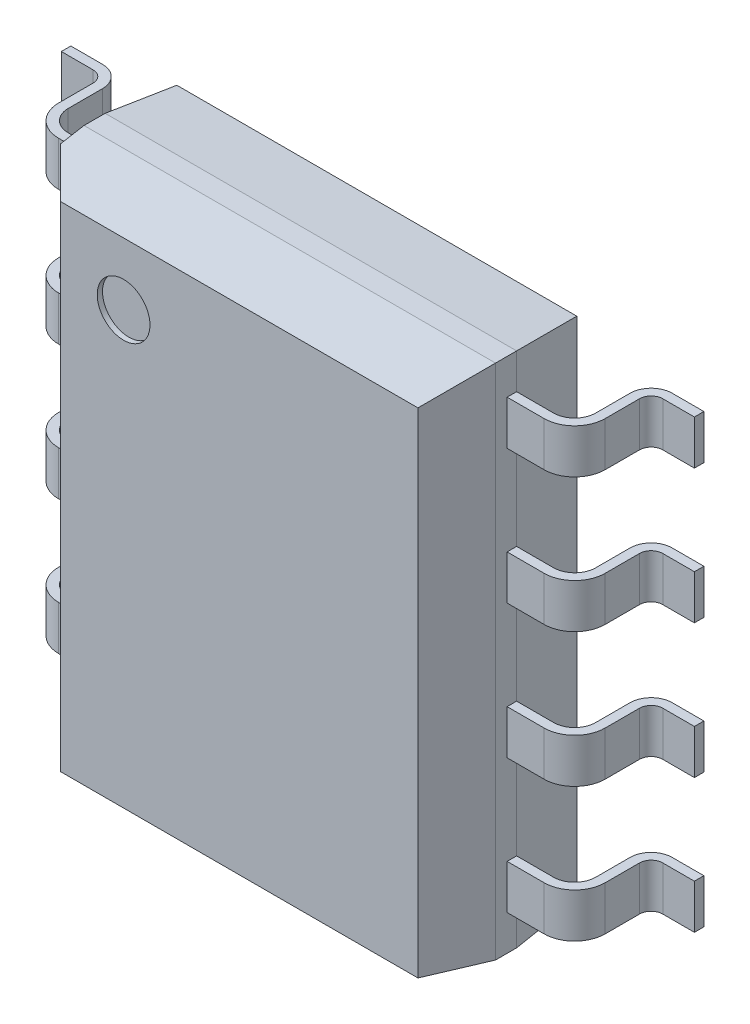
SolidWorks part; units mm, degrees
ref_plane "Face" through (0, 0, 0) normal (0, 0, 1) x (1, 0, 0)
ref_plane "Dessus" through (0, 0, 0) normal (0, 1, 0) x (1, 0, 0)
ref_plane "Droite" through (0, 0, 0) normal (1, 0, 0) x (0, 0, -1)
ref_plane "fond circuit" through (0, 0, 0.1) normal (0, 0, 1) x (1, 0, 0)
sketch "Esquisse2" plane through (0, 0, 0.1) normal (0, 0, 1) x (1, 0, 0)
  line L1 (-1.95, 2.45) -> (1.95, 2.45)
  line L2 (-1.95, 2.45) -> (-1.95, -2.45)
  line L3 (-1.95, -2.45) -> (1.95, -2.45)
  line L4 (1.95, 2.45) -> (1.95, -2.45)
  point P4 (1.95, 0)
  point P6 (0, 2.45)
  dimension "D1" = 3.9
  dimension "D2" = 4.9
extrude "corp" add sketch "Esquisse2" along normal blind 1.45
ref_plane "plan pin 1" through (0, 1.905, 0) normal (0, 1, 0) x (-1, 0, 0)
sketch "Esquisse6" plane through (0, 1.905, 0) normal (0, 1, 0) x (-1, 0, 0)
  line L0 (0, 0) -> (6.8831, 0) construction
  line L1 (1.95, 0.725) -> (2.3, 0.725)
  line L2 (1.95, 1.55) -> (1.95, 0.1) construction
  line L3 (2.5, 0.525) -> (2.5, 0.2)
  line L4 (3, 0) -> (2.7, 0)
  line L6 (-1.95, 1.55) -> (1.95, 1.55) construction
  arc A0 (2.3, 0.725) -> (2.5, 0.525) centre (2.3, 0.525) cw
  arc A1 (2.7, 0) -> (2.5, 0.2) centre (2.7, 0.2) cw
  dimension "D1" = 0.2
  dimension "D2" = 0.5
  dimension "D3" = 1.05
  dimension "D4" = 0.825
extrude "pin 1" add sketch "Esquisse6" along normal mid plane 0.42 thin thin type one direction wall 0.09
pattern_linear "Répétition pin 1-4" count 4 spacing 1.27 along (0, -1, 0) of "pin 1"
mirror "Symétrie1" about plane through (0, 0, 0) normal (1, 0, 0) of "Répétition pin 1-4"
ref_plane "Plan2" through (3.75, 0, 0) normal (1, 0, 0) x (0, 0, -1)
chamfer "Chanfrein4" distance 0.625 angle 10 3 edges at (0, 2.45, 1.55) (1.95, 0, 1.55) (0, -2.45, 1.55) first distance on face at (0, 2.45, 0.825) first distance on face at (1.95, -1.905, 0.77) first distance on face at (0, -2.45, 0.825)
chamfer "Chanfrein5" distance 0.625 angle 5 4 edges at (0, -2.45, 0.1) (1.95, 0, 0.1) (0, 2.45, 0.1) (-1.95, 0, 0.1) first distance on face at (0, -2.45, 0.5125) first distance on face at (1.95, -1.905, 0.77) first distance on face at (0, 2.45, 0.5125) first distance on face at (-1.95, -1.905, 0.77)
sketch "Esquisse8" plane through (0, 0, 1.55) normal (0, 0, 1) x (1, 0, 0)
  line L0 (-1.95, 2.45) -> (-1.95, 2.115) construction
  line L3 (-1.95, 2.45) -> (1.95, 2.45) construction
  circle A0 centre (-0.95, 1.75) radius 0.25
  dimension "D1" = 0.5
  dimension "D2" = 1
  dimension "D3" = 0.7
extrude "Enlèv. mat.-Extru.1" cut sketch "Esquisse8" against normal blind 0.05
chamfer "Chanfrein7" distance 0.4 angle 45 1 edges at (-1.95, 0, 1.55)
sketch "Esquisse9" plane through (0, 0, 0.1) normal (0, 0, -1) x (-1, 0, 0)
  line L1 (-1.05, 1.05) -> (1.05, 1.05)
  line L2 (-1.05, 1.05) -> (-1.05, -1.05)
  line L3 (-1.05, -1.05) -> (1.05, -1.05)
  line L4 (1.05, 1.05) -> (1.05, -1.05)
  line L5 (-1.05, 1.05) -> (1.05, -1.05) construction
  line L6 (-1.05, -1.05) -> (1.05, 1.05) construction
  point P0 (0, 0)
  dimension "D1" = 2.1
  dimension "D2" = 2.1
extrude "exposed pad" add sketch "Esquisse9" along normal blind 0.1
